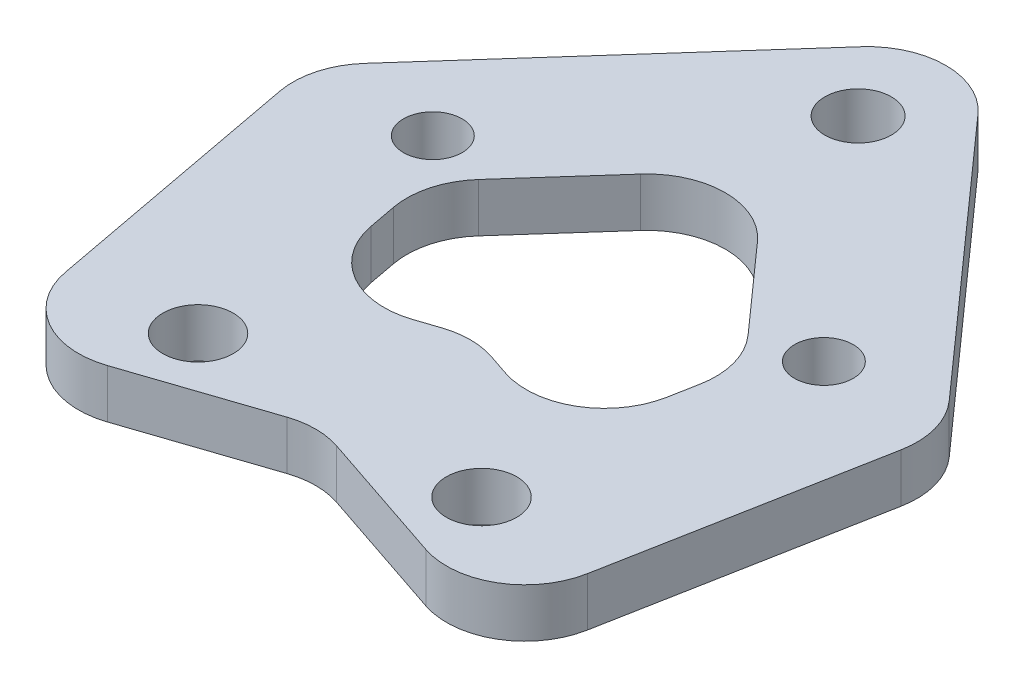
SolidWorks part; units mm, degrees
ref_plane "Front Plane" through (0, 0, 0) normal (0, 0, 1) x (1, 0, 0)
ref_plane "Top Plane" through (0, 0, 0) normal (0, 1, 0) x (1, 0, 0)
ref_plane "Right Plane" through (0, 0, 0) normal (1, 0, 0) x (0, 0, -1)
sketch "Sketch1" plane through (0, 0, 0) normal (0, 1, 0) x (1, 0, 0)
  line L0 (0, 20.0025) -> (64.77, 20.0025) construction
  line L5 (0, 38.0694) -> (0, 1.9356) construction
  line L10 (11.7475, 20.0025) -> (32.385, 43.18)
  line L11 (32.385, 43.18) -> (53.0225, 20.0025)
  line L12 (11.7475, 20.0025) -> (16.51, -5.3509)
  line L13 (64.77, 38.0694) -> (64.77, 1.9356) construction
  line L19 (48.26, -5.3509) -> (53.0225, 20.0025)
  line L22 (16.51, -5.3509) -> (32.385, -0.0231)
  line L23 (32.385, -0.0231) -> (48.26, -5.3509)
  arc A0 (32.5724, -0.0455) -> (32.1976, -0.0455) centre (32.385, -0.8168) ccw construction
  point P6 (32.385, -0.0231)
  point P17 (32.385, 40.0281)
  point P18 (32.385, 44.036)
  point P21 (0, 0)
  point P23 (0, 0)
  dimension "D1" = 41.275
  dimension "D2" = 31.75
  dimension "D3" = 25.7969
  dimension "D4" = 23.1775
extrude "Boss-Extrude1" add sketch "Sketch1" along normal mid plane 3.175
sketch "Sketch2" plane through (0, -1.5875, 0) normal (0, 1, 0) x (1, 0, 0)
  line L4 (32.385, 43.18) -> (32.385, -0.0231) construction
  line L6 (-187.96, 40.005) -> (0, 40.005) construction
  circle A0 centre (19.685, 20.0025) radius 1.905
  circle A1 centre (45.085, 20.0025) radius 1.905
  circle A2 centre (19.685, 20.0025) radius 2.286 construction
  circle A3 centre (45.085, 20.0025) radius 7.239 construction
  circle A5 centre (32.385, 34.925) radius 2.159
  circle A8 centre (23.1775, 1.2597) radius 2.286
  circle A10 centre (41.5925, 1.2597) radius 2.286
  point P10 (32.385, 21.5785)
  dimension "D1" = 3.81
  dimension "D7" = 4.318
  dimension "D4" = 9.2075
  dimension "D5" = 4.572
  dimension "D3" = 5.08
  dimension "D6" = 20.3188
extrude "Cut-Extrude1" cut sketch "Sketch2" along normal through all
sketch "Sketch4" plane through (0, 1.5875, 0) normal (0, 1, 0) x (1, 0, 0)
  line L33 (21.9725, 17.1627) -> (23.8515, 7.1601)
  line L34 (23.8515, 7.1601) -> (32.385, 10.024)
  line L35 (32.385, 10.024) -> (40.9185, 7.1601)
  line L36 (40.9185, 7.1601) -> (42.7975, 17.1627)
  line L37 (42.7975, 17.1627) -> (32.385, 28.8567)
  line L38 (32.385, 28.8567) -> (21.9725, 17.1627)
  line L39 (21.9725, 17.1627) -> (23.8515, 7.1601)
  line L40 (23.8515, 7.1601) -> (32.385, 10.024)
  line L41 (32.385, 10.024) -> (40.9185, 7.1601)
  line L42 (40.9185, 7.1601) -> (42.7975, 17.1627)
  line L43 (42.7975, 17.1627) -> (32.385, 28.8567)
  line L44 (32.385, 28.8567) -> (21.9725, 17.1627)
  dimension "D1" = 9.525
extrude "Cut-Extrude3" cut sketch "Sketch4" against normal through all
fillet "Fillet2" radius 5.08 12 edges at (23.8515, 0, -7.1601) (32.385, 0, -10.024) (40.9185, 0, -7.1601) (42.7975, 0, -17.1627) (32.385, 0, -28.8567) (21.9725, 0, -17.1627) (11.7475, 0, -20.0025) (32.385, 0, -43.18) (53.0225, 0, -20.0025) (32.385, 0, 0.0231) (16.51, 0, 5.3509) (48.26, 0, 5.3509)
